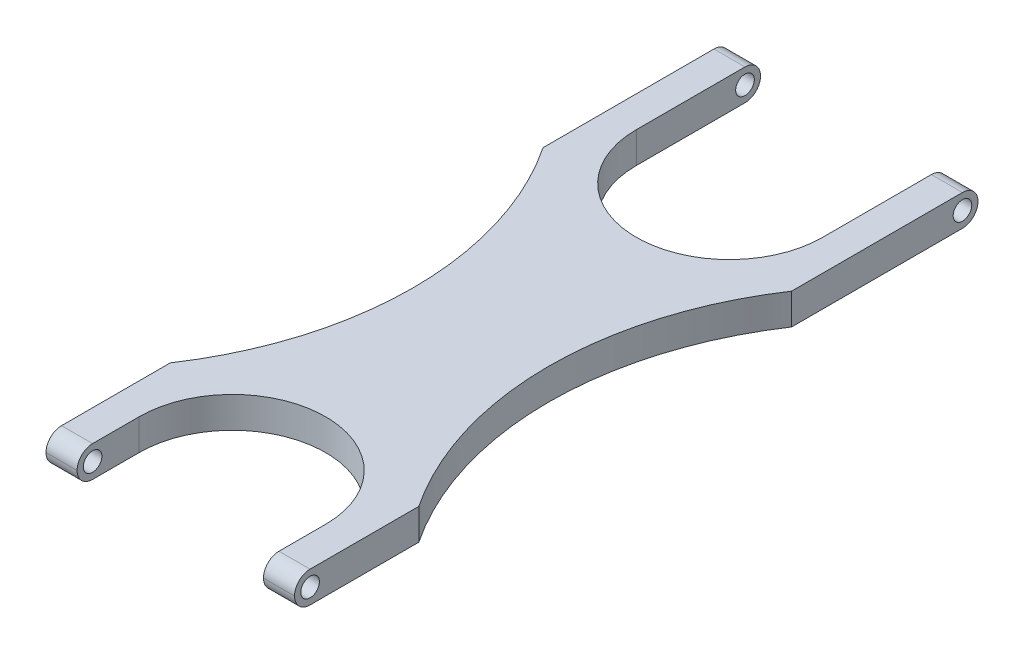
SolidWorks part; units mm, degrees
ref_plane "Front Plane" through (0, 0, 0) normal (0, 0, 1) x (1, 0, 0)
ref_plane "Top Plane" through (0, 0, 0) normal (0, 1, 0) x (1, 0, 0)
ref_plane "Right Plane" through (0, 0, 0) normal (1, 0, 0) x (0, 0, -1)
sketch "Sketch1" plane through (0, 0, 0) normal (0, 1, 0) x (1, 0, 0)
  line L0 (0, 0) -> (12.7, 0)
  line L1 (12.7, 0) -> (12.7, -50.8)
  line L2 (0, 0) -> (0, -76.2)
  line L3 (0, -228.6) -> (0, -279.4)
  line L4 (0, -279.4) -> (12.7, -279.4)
  line L5 (12.7, -279.4) -> (12.7, -254)
  line L6 (50.8, -88.9) -> (50.8, -215.9) construction
  line L7 (88.9, -279.4) -> (88.9, -254)
  line L8 (101.6, -279.4) -> (88.9, -279.4)
  line L9 (101.6, -228.6) -> (101.6, -279.4)
  line L10 (101.6, 0) -> (101.6, -76.2)
  line L11 (88.9, 0) -> (88.9, -50.8)
  line L12 (101.6, 0) -> (88.9, 0)
  arc A0 (12.7, -50.8) -> (50.8, -88.9) centre (50.8, -50.8) ccw
  arc A1 (0, -76.2) -> (0, -228.6) centre (-114.3, -152.4) cw
  arc A2 (12.7, -254) -> (50.8, -215.9) centre (50.8, -254) cw
  arc A3 (88.9, -254) -> (50.8, -215.9) centre (50.8, -254) ccw
  arc A4 (88.9, -50.8) -> (50.8, -88.9) centre (50.8, -50.8) cw
  arc A5 (101.6, -76.2) -> (101.6, -228.6) centre (215.9, -152.4) ccw
  dimension "D8" = 330.2
  dimension "D1" = 279.4
  dimension "D2" = 12.7
  dimension "D3" = 76.2
  dimension "D4" = 50.8
  dimension "D5" = 25.4
  dimension "D6" = 76.2
  dimension "D7" = 50.8
extrude "Boss-Extrude1" add sketch "Sketch1" along normal blind 12.7
fillet "Fillet1" radius 6.35 8 edges at (95.25, 0, 0) (6.35, 0, 0) (95.25, 12.7, 0) (6.35, 12.7, 0) (6.35, 0, 279.4) (6.35, 12.7, 279.4) (95.25, 0, 279.4) (95.25, 12.7, 279.4)
sketch "Sketch2" plane through (101.6, 0, 0) normal (1, 0, 0) x (0, 0, -1)
  circle A0 centre (-273.05, 6.35) radius 3.81
extrude "Cut-Extrude1" cut sketch "Sketch2" against normal through all
sketch "Sketch3" plane through (101.6, 0, 0) normal (1, 0, 0) x (0, 0, -1)
  circle A0 centre (-6.35, 6.35) radius 3.81
extrude "Cut-Extrude2" cut sketch "Sketch3" against normal through all
